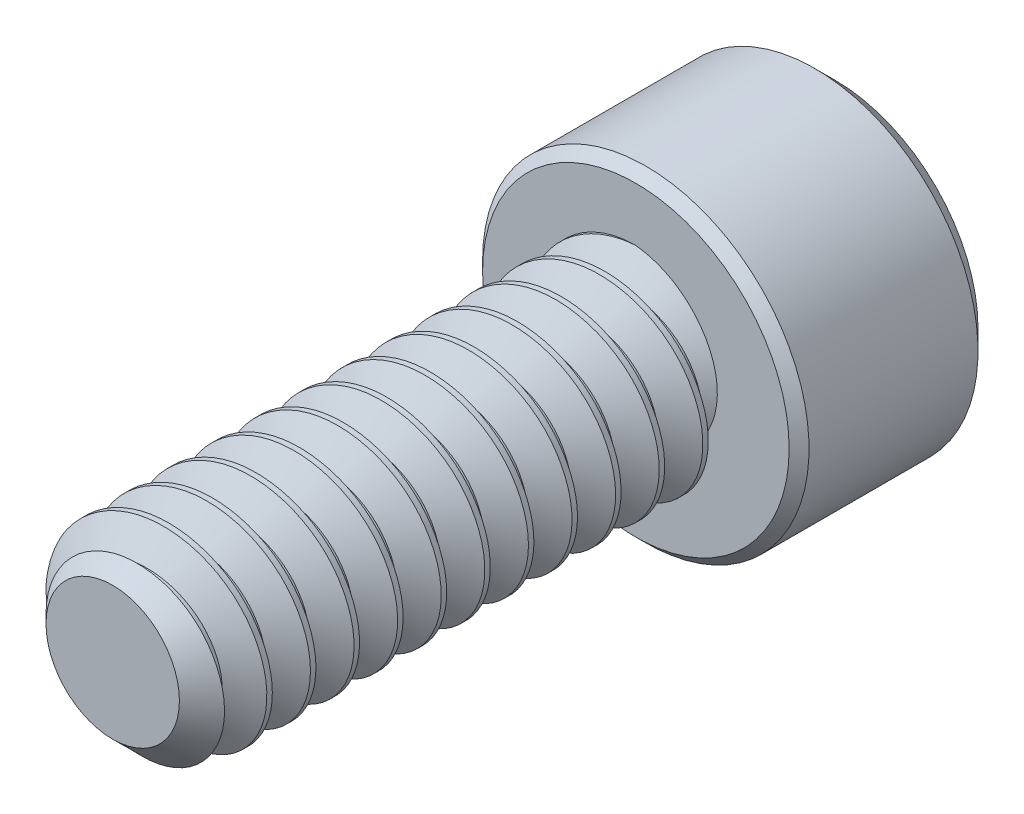
SolidWorks part; units mm, degrees
ref_plane "Front Plane" through (0, 0, 0) normal (0, 0, 1) x (1, 0, 0)
ref_plane "Top Plane" through (0, 0, 0) normal (0, 1, 0) x (1, 0, 0)
ref_plane "Right Plane" through (0, 0, 0) normal (1, 0, 0) x (0, 0, -1)
sketch "Sketch1" plane through (0, 0, 0) normal (0, 0, 1) x (1, 0, 0)
  line L0 (0, 2.413) -> (0, -2.413) construction
  circle A0 centre (0, 0) radius 2.413
  dimension "OD" = 4.826
extrude "Extrude1" add sketch "Sketch1" against normal blind 12.7
sketch "Sketch2" plane through (0, 0, 0) normal (0, 0, 1) x (1, 0, 0)
  circle A0 centre (0, 0) radius 2.413 construction
  circle A1 centre (0, 0) radius 2.413
curve "Helix/Spiral1" pitch 1.0583 height 13.7583 turns 13 parameters "pitch"=1.0583
chamfer "Chamfer3" distance 0.7937 angle 45 1 edges at (2.413, 0, 0)
sketch "Sketch3" plane through (0, 0, 0) normal (1, 0, 0) x (0, 0, -1)
  line L0 (-0.926, 2.413) -> (-0.5292, 1.7256)
  line L1 (-0.5292, 1.7256) -> (-0.3969, 1.7256)
  line L2 (-0.3969, 1.7256) -> (0, 2.413)
  line L3 (-0.926, 2.413) -> (0, 2.413)
  line L4 (-0.463, 2.413) -> (-0.463, 1.7256) construction
  line L5 (-0.7276, 2.0693) -> (-0.1984, 2.0693) construction
  line L6 (0, 2.413) -> (0, -2.413) construction
  dimension "D1" = 0.1323
  dimension "D2" = 0.5292
  dimension "D3" = 60
sweep "Cut-Sweep1" cut profiles "Sketch3" path "Helix/Spiral1"
sketch "Sketch6" plane through (0, 0, -12.7) normal (0, 0, -1) x (-1, 0, 0)
  circle A0 centre (0, 0) radius 3.9624
  dimension "head dia" = 7.9248
extrude "Extrude2" add sketch "Sketch6" along normal blind 4.826
sketch "Sketch7" [suppressed] plane through (0, 0, -17.526) normal (0, 0, -1) x (-1, 0, 0)
  line L1 (0, 2.2914) -> (-1.9844, 1.1457)
  line L2 (-1.9844, 1.1457) -> (-1.9844, -1.1457)
  line L3 (-1.9844, -1.1457) -> (0, -2.2914)
  line L4 (0, -2.2914) -> (1.9844, -1.1457)
  line L5 (1.9844, -1.1457) -> (1.9844, 1.1457)
  line L6 (1.9844, 1.1457) -> (0, 2.2914)
  circle A0 centre (0, 0) radius 1.9844 construction
  dimension "hex dia" = 3.9688
extrude "Cut-Extrude1" [suppressed] cut sketch "Sketch7" against normal blind 2.9766
sketch "Sketch8" [suppressed] plane through (0, 0, -17.526) normal (0, 0, -1) x (-1, 0, 0)
  circle A0 centre (0, 0) radius 2.2914
extrude "Cut-Extrude2" [suppressed] cut sketch "Sketch8" against normal blind 0.4826 draft 45
chamfer "Chamfer1" distance 0.4826 angle 45 1 edges at (-3.9624, 0, -17.526)
chamfer "Chamfer2" distance 0.2413 angle 45 1 edges at (-3.9624, 0, -12.7)
sketch "Sketch9" [suppressed] plane through (0, 0, 0) normal (1, 0, 0) x (0, 0, -1)
  line L0 (0, 2.413) -> (0, -2.413) construction
  line L1 (5.8208, 2.413) -> (5.8208, -2.413) construction
  line L2 (12.7, 3.9624) -> (12.7, -3.9624) construction
  line L3 (17.526, 3.9624) -> (17.526, -3.9624) construction
  line L4 (17.526, 0) -> (0, 0) construction
  dimension "D1" = 5.8208
  dimension "D2" = 4.826
  dimension "D3" = 7.9248
  dimension "D4" = 12.7
equation "\"D3@Helix/Spiral1\" = \"screw length@Extrude1\"+\"pitch@Helix/Spiral1\""
equation "\"D1@Sketch3\" = \"pitch@Helix/Spiral1\"*.125"
equation "\"D2@Sketch3\" = \"pitch@Helix/Spiral1\"*.5"
equation "\"D1@Cut-Extrude1\" = \"hex dia@Sketch7\"*.75"
equation "\"D1@Chamfer1\" = \"head depth@Extrude2\"/10"
equation "\"D1@Sketch9\" = \"pitch@Helix/Spiral1\"*5.5"
equation "\"D1@Chamfer2\" = \"D1@Chamfer1\"/2"
equation "\"D1@Cut-Extrude2\" = \"D1@Chamfer2\"*2"
equation "\"D1@Chamfer3\" = \"pitch@Helix/Spiral1\"*.750"
equation "\"D2@Sketch9\" = \"head depth@Extrude2\""
equation "\"D3@Sketch9\" = \"head dia@Sketch6\""
equation "\"D4@Sketch9\" = \"screw length@Extrude1\""
